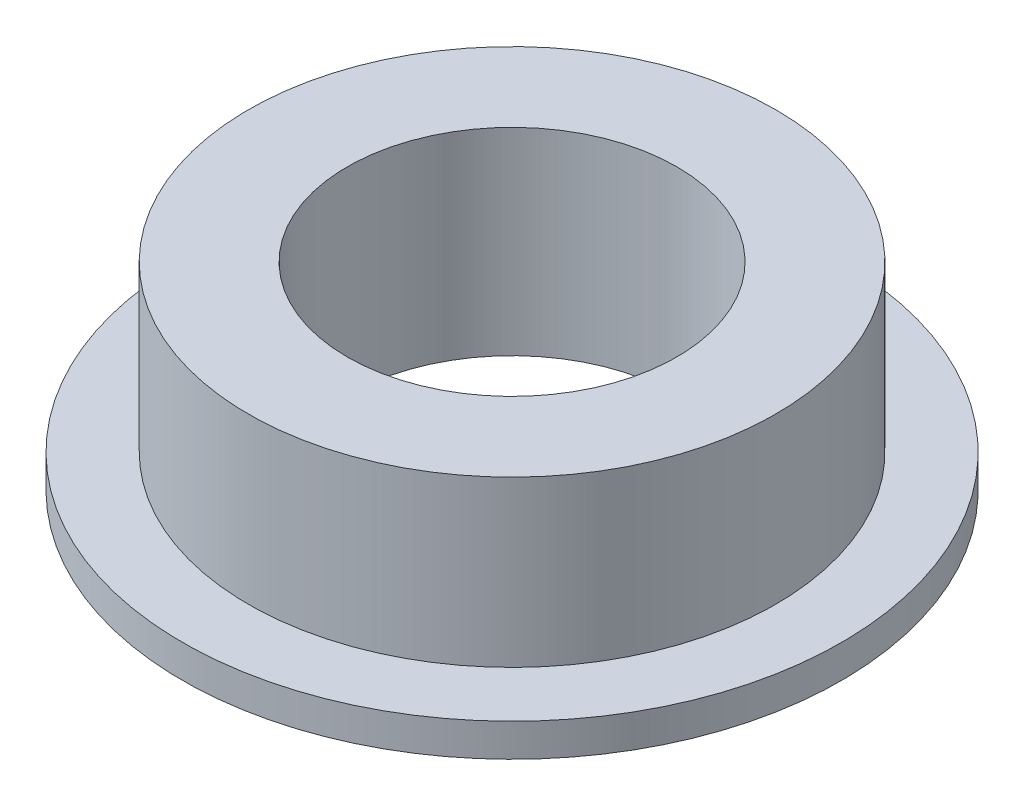
SolidWorks part; units mm, degrees
material "Alum Plate"
ref_plane "Front Plane" through (0, 0, 0) normal (0, 0, 1) x (1, 0, 0)
ref_plane "Top Plane" through (0, 0, 0) normal (0, 1, 0) x (1, 0, 0)
ref_plane "Right Plane" through (0, 0, 0) normal (1, 0, 0) x (0, 0, -1)
other "Bounding Box"
ref_plane "Default Plane" through (-8.9266, -12.7485, 0) normal (-0.1736, 0.9848, 0) x (0.9848, 0.1736, 0)
sketch "Sketch1" plane through (0, 0, 0) normal (0, 1, 0) x (1, 0, 0)
  circle A0 centre (0, 0) radius 7.9375
  circle A1 centre (0, 0) radius 12.7
  dimension "D1" = 15.875
  dimension "D2" = 25.4
extrude "Boss-Extrude1" add sketch "Sketch1" along normal mid plane 9.525
sketch "Sketch2" plane through (0, -4.7625, 0) normal (0, -1, 0) x (1, 0, 0)
  circle A0 centre (0, 0) radius 15.875
  circle A1 centre (0, 0) radius 12.7 construction
  circle A2 centre (0, 0) radius 12.7
  dimension "D1" = 31.75
extrude "Boss-Extrude2" add sketch "Sketch2" against normal blind 1.5875
